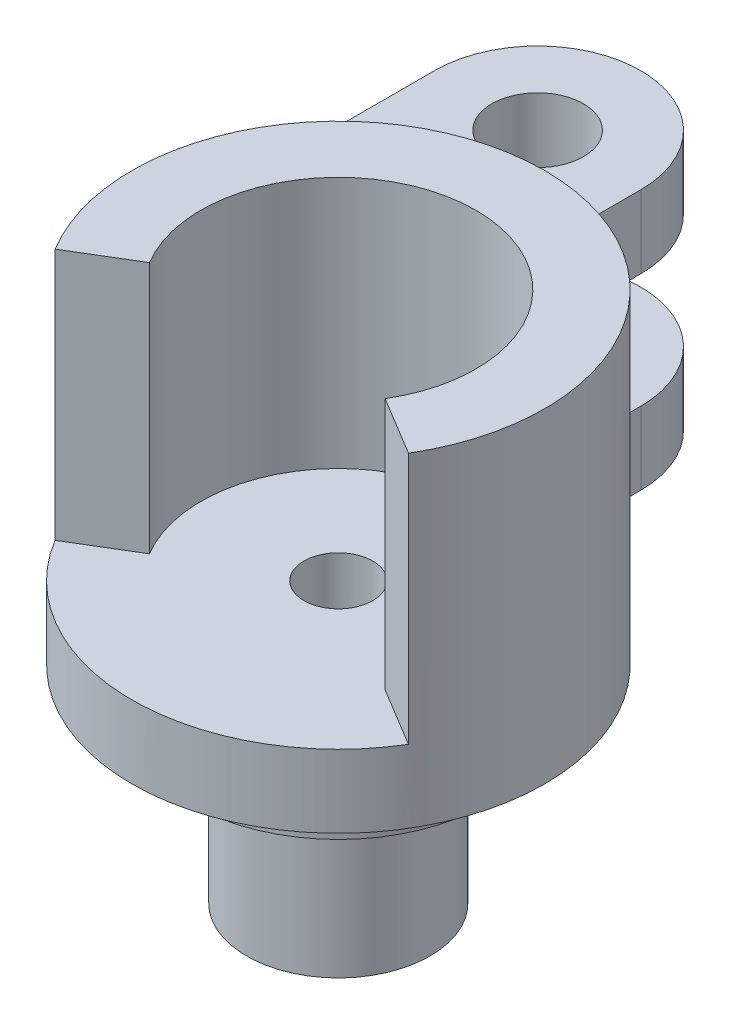
SolidWorks part; units mm, degrees
ref_plane "Front Plane" through (0, 0, 0) normal (0, 0, 1) x (1, 0, 0)
ref_plane "Top Plane" through (0, 0, 0) normal (0, 1, 0) x (1, 0, 0)
ref_plane "Right Plane" through (0, 0, 0) normal (1, 0, 0) x (0, 0, -1)
sketch "Sketch1" plane through (0, 0, 0) normal (0, 1, 0) x (1, 0, 0)
  circle A0 centre (0, 0) radius 9
  dimension "D1" = 18
extrude "Boss-Extrude1" add sketch "Sketch1" along normal blind 3.175
sketch "Sketch2" plane through (0, 3.175, 0) normal (0, 1, 0) x (1, 0, 0)
  line L0 (-7.7077, -4.6466) -> (-5.1385, -3.0978)
  line L1 (-7.7077, -4.6466) -> (7.7077, -4.6466) construction
  line L3 (5.1385, -3.0978) -> (7.7077, -4.6466)
  arc A0 (-7.7077, -4.6466) -> (7.7077, -4.6466) centre (0, 0) cw
  circle A1 centre (0, 0) radius 9 construction
  arc A2 (-5.1385, -3.0978) -> (5.1385, -3.0978) centre (0, 0) cw
  dimension "D1" = 117.832
  dimension "D2" = 3
extrude "Boss-Extrude2" add sketch "Sketch2" along normal blind 11
sketch "Sketch3" plane through (0, 0, 0) normal (0, -1, 0) x (1, 0, 0)
  circle A0 centre (0, 0) radius 6.5
  dimension "D1" = 13
extrude "Boss-Extrude3" add sketch "Sketch3" along normal blind 2
sketch "Sketch4" plane through (0, -2, 0) normal (0, -1, 0) x (1, 0, 0)
  circle A0 centre (0, 0) radius 4
  dimension "D1" = 8
extrude "Boss-Extrude4" add sketch "Sketch4" along normal blind 7
sketch "Sketch6" plane through (0, 0, 0) normal (0, 1, 0) x (1, 0, 0)
  line L0 (-9, 0) -> (-9, 13.1942)
  line L1 (0, 9) -> (0, 13.1942)
  arc A0 (7.7077, -4.6466) -> (-7.7077, -4.6466) centre (0, 0) ccw construction
  arc A1 (0, 13.1942) -> (-9, 13.1942) centre (-4.5, 13.1942) ccw
  arc A2 (0, 9) -> (-9, 0) centre (0, 0) ccw
  point P10 (-4.5, 17.6942)
  dimension "D1" = 8.6942
extrude "Boss-Extrude5" add sketch "Sketch6" along normal up to surface (3.175 mm away) up to face at (0, 3.175, 2.6861)
ref_plane "Plane1" through (0, 8.175, 0) normal (0, 1, 0) x (1, 0, 0)
sketch "Sketch7" plane through (0, 8.175, 0) normal (0, 1, 0) x (1, 0, 0)
  line L0 (0, 9) -> (0, 13.1942) construction
  line L1 (-9, 13.1942) -> (-9, 0) construction
  line L2 (0, 9) -> (0, 13.1942)
  line L3 (-9, 13.1942) -> (-9, 0)
  arc A0 (0, 9) -> (-9, 0) centre (0, 0) ccw construction
  arc A1 (0, 13.1942) -> (-9, 13.1942) centre (-4.5, 13.1942) ccw construction
  arc A2 (0, 9) -> (-9, 0) centre (0, 0) ccw
  arc A3 (0, 13.1942) -> (-9, 13.1942) centre (-4.5, 13.1942) ccw
extrude "Boss-Extrude7" add sketch "Sketch7" along normal blind 3.175
sketch "Sketch8" plane through (0, 11.35, 0) normal (0, 1, 0) x (1, 0, 0)
  circle A0 centre (-4.5, 13.1942) radius 2
  arc A1 (0, 13.1942) -> (-9, 13.1942) centre (-4.5, 13.1942) ccw construction
  dimension "D1" = 4
extrude "Cut-Extrude1" cut sketch "Sketch8" against normal up to surface (11.35 mm away) up to face at (0, 0, -6.5)
sketch "Sketch9" plane through (0, 3.175, 0) normal (0, 1, 0) x (1, 0, 0)
  circle A0 centre (0, 0) radius 1.5
  dimension "D1" = 3
extrude "Cut-Extrude2" cut sketch "Sketch9" against normal up to surface (12.175 mm away) contours A0 up to face at (0, -9, -4)
